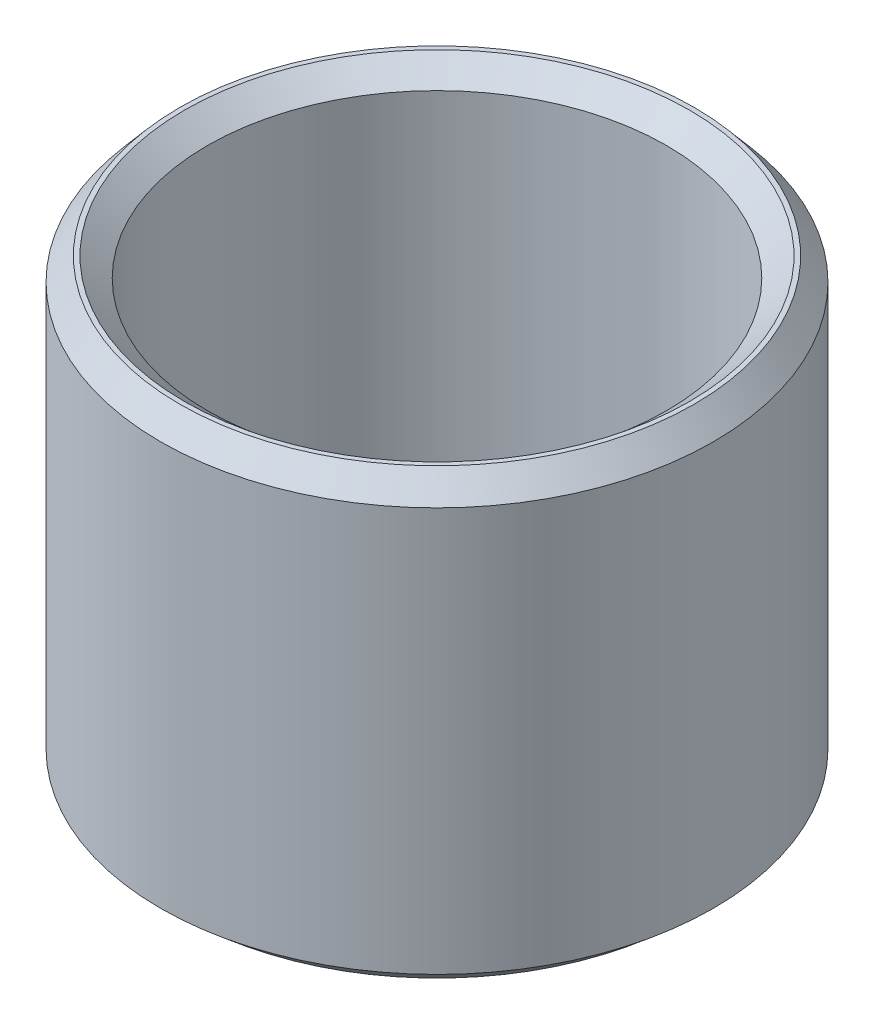
SolidWorks part; units mm, degrees
ref_plane "Front Plane" through (0, 0, 0) normal (0, 0, 1) x (1, 0, 0)
ref_plane "Top Plane" through (0, 0, 0) normal (0, 1, 0) x (1, 0, 0)
ref_plane "Right Plane" through (0, 0, 0) normal (1, 0, 0) x (0, 0, -1)
sketch "Sketch1" plane through (0, 0, 0) normal (0, 1, 0) x (1, 0, 0)
  circle A0 centre (0, 0) radius 42.5
  dimension "SLEEVE_OD" = 85
extrude "Boss-Extrude1" add sketch "Sketch1" along normal blind 68.5882
sketch "Sketch2" plane through (0, 0, 0) normal (0, 1, 0) x (1, 0, 0)
  circle A0 centre (0, 0) radius 35.3048
  dimension "BORE_D" = 70.6097
extrude "Cut-Extrude1" cut sketch "Sketch2" along normal through all
chamfer "Chamfer1" distance 3.5042 angle 40.283 4 edges at (0, 68.5882, 35.3048) (0, 0, 35.3048) (0, 0, 42.5) (0, 68.5882, 42.5) first distance on face at (0, 68.5882, 35.3048) first distance on face at (0, 0, 35.3048) first distance on face at (0, 68.5882, 42.5)
